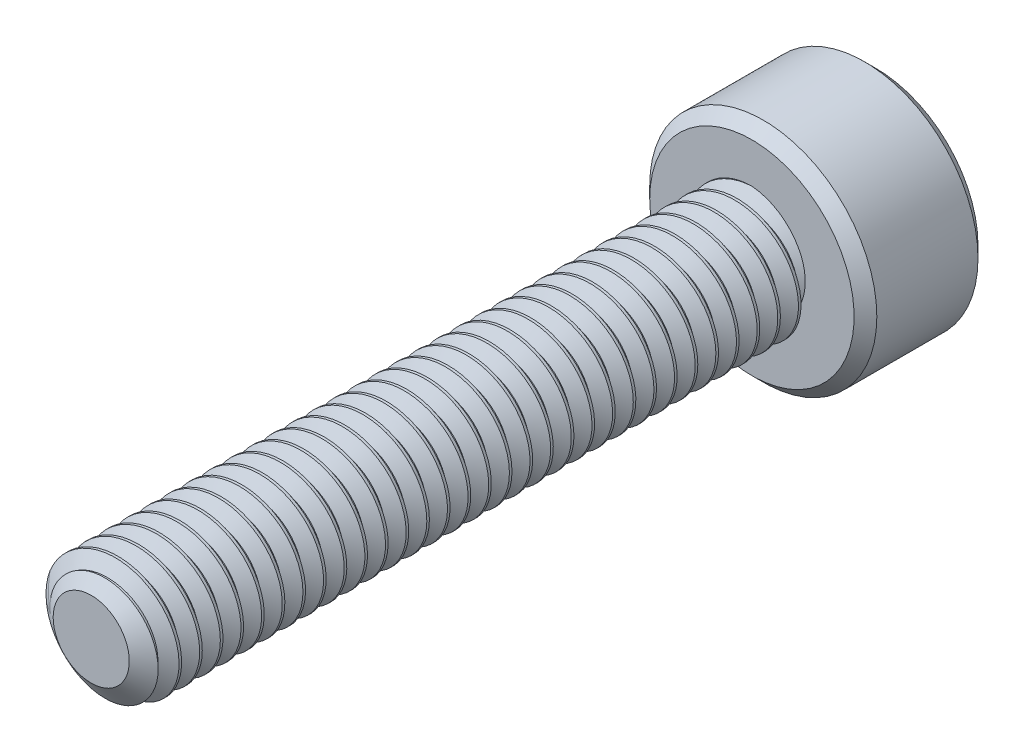
SolidWorks part; units mm, degrees
other "DetailItem1"
ref_plane "Front Plane" through (0, 0, 0) normal (0, 0, 1) x (1, 0, 0)
ref_plane "Top Plane" through (0, 0, 0) normal (0, 1, 0) x (1, 0, 0)
ref_plane "Right Plane" through (0, 0, 0) normal (1, 0, 0) x (0, 0, -1)
sketch "Sketch1" plane through (0, 0, 0) normal (0, 0, 1) x (1, 0, 0)
  circle A0 centre (0, 0) radius 1.5
  dimension "OD" = 3
extrude "Extrude1" add sketch "Sketch1" against normal blind 16
sketch "Sketch2" plane through (0, 0, 0) normal (0, 0, 1) x (1, 0, 0)
  circle A0 centre (0, 0) radius 1.5 construction
  circle A1 centre (0, 0) radius 1.5
curve "Helix/Spiral1" pitch 0.5 height 16.5 radius 1.5 centre (0, 0, 0) axis (0, 0, -1) start towards (0, 1, 0) parameters "pitch"=0.5
sketch "Sketch3" plane through (0, 0, 0) normal (1, 0, 0) x (0, 0, -1)
  line L0 (-0.4375, 1.5) -> (-0.25, 1.1752)
  line L1 (-0.25, 1.1752) -> (-0.1875, 1.1752)
  line L2 (-0.1875, 1.1752) -> (0, 1.5)
  line L3 (-0.4375, 1.5) -> (0, 1.5)
  line L4 (-0.2187, 1.5) -> (-0.2188, 1.1752) construction
  line L5 (-0.3438, 1.3376) -> (-0.0938, 1.3376) construction
  line L6 (0, 1.5) -> (0, -1.5) construction
  dimension "D1" = 0.0625
  dimension "D2" = 0.25
  dimension "D3" = 60
sweep "Cut-Sweep1" cut profiles "Sketch3" path "Helix/Spiral1" align with end faces yes
sketch "Sketch4" plane through (0, 0, 0) normal (1, 0, 0) x (0, 0, -1)
  line L0 (0.4053, 1.5) -> (0, 0.9212)
  line L1 (0, 0.9212) -> (0, 1.5)
  line L2 (0.4053, 1.5) -> (0, 1.5)
  line L3 (-0.4375, 1.5) -> (0, 1.5) construction
  line L4 (0, 0) -> (7.0209, 0) construction
  dimension "D1" = 55
  dimension "D2" = 0.254
revolve "Cut-Revolve1" cut sketch "Sketch4" angle 360 about L4
sketch "Sketch6" plane through (0, 0, -16) normal (0, 0, -1) x (-1, 0, 0)
  circle A0 centre (0, 0) radius 2.75
  dimension "head dia" = 5.5
extrude "Extrude2" add sketch "Sketch6" along normal blind 3
sketch "Sketch7" plane through (0, 0, -19) normal (0, 0, -1) x (-1, 0, 0)
  line L1 (0, 1.4434) -> (-1.25, 0.7217)
  line L2 (-1.25, 0.7217) -> (-1.25, -0.7217)
  line L3 (-1.25, -0.7217) -> (0, -1.4434)
  line L4 (0, -1.4434) -> (1.25, -0.7217)
  line L5 (1.25, -0.7217) -> (1.25, 0.7217)
  line L6 (1.25, 0.7217) -> (0, 1.4434)
  circle A0 centre (0, 0) radius 1.25 construction
  dimension "hex dia" = 2.5
extrude "Cut-Extrude1" cut sketch "Sketch7" against normal blind 1.875
sketch "Sketch8" plane through (0, 0, -19) normal (0, 0, -1) x (-1, 0, 0)
  circle A0 centre (0, 0) radius 1.4434
extrude "Cut-Extrude2" cut sketch "Sketch8" against normal through all draft 45
chamfer "Chamfer1" distance 0.275 angle 45 2 edges at (-2.75, 0, -19) (-2.75, 0, -16)
sketch "Sketch10" plane through (0, 0, -16) normal (0, 0, 1) x (1, 0, 0)
  circle A1 centre (0, 0) radius 1.5
  circle A2 centre (0, 0) radius 1.5
  dimension "D1" = 0
ref_plane "Plane1" through (0, 0, 0) normal (0, 0, 1) x (1, 0, 0)
extrude "partial thread" [suppressed] add sketch "Sketch10" along normal up to surface (4 mm away) separate body up to plane "Plane1"
chamfer "Chamfer2" [suppressed] distance 0.06 angle 45
combine bodies "Combine1" [suppressed] operation type add bodies to combine 107 108
sketch "Sketch9" plane through (0, 0, 0) normal (1, 0, 0) x (0, 0, -1)
  line L0 (0, 1.5) -> (0, -1.5) construction
  line L1 (1.25, 1.5) -> (1.25, -1.5) construction
  dimension "D1" = 1.25
equation "\"D3@Helix/Spiral1\" = \"screw length@Extrude1\"+\"pitch@Helix/Spiral1\""
equation "\"D1@Sketch3\" = \"pitch@Helix/Spiral1\"*.125"
equation "\"D2@Sketch3\" = \"pitch@Helix/Spiral1\"*.5"
equation "\"D1@Cut-Extrude1\" = \"hex dia@Sketch7\"*.75"
equation "\"D1@Chamfer1\" = \"head dia@Sketch6\"*.05"
equation "\"D1@Sketch9\" = \"pitch@Helix/Spiral1\"*2.5"
equation "\"D1@Chamfer2\"=\"OD@Sketch1\"*.02"
